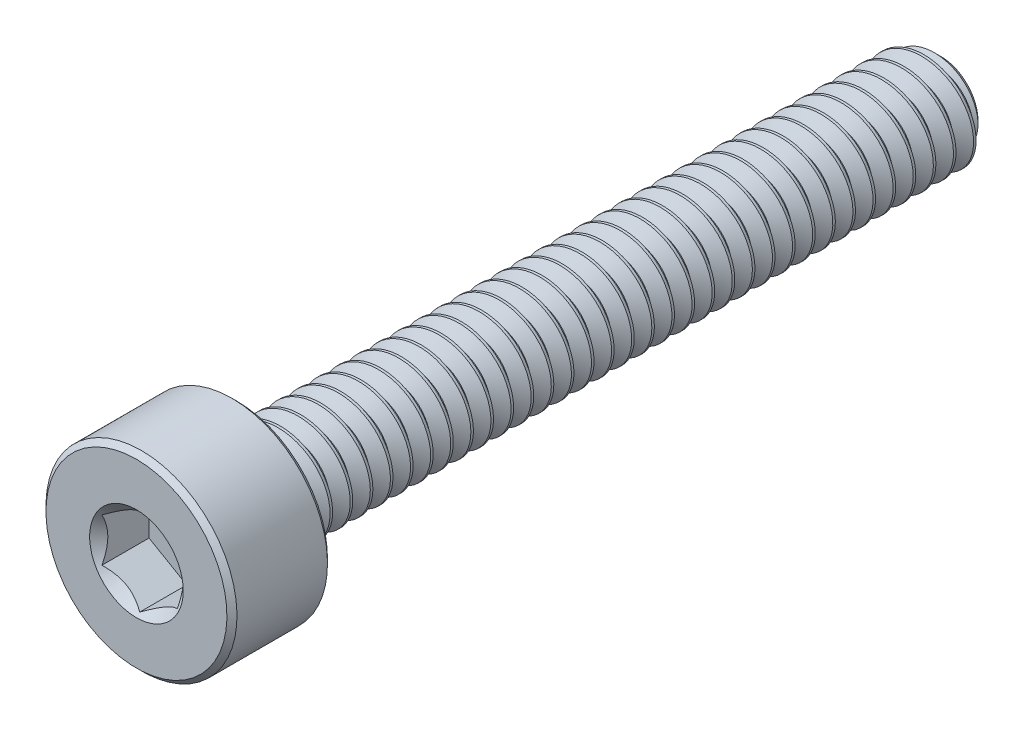
SolidWorks part; units mm, degrees
ref_plane "Front Plane" through (0, 0, 0) normal (0, 0, 1) x (1, 0, 0)
ref_plane "Top Plane" through (0, 0, 0) normal (0, 1, 0) x (1, 0, 0)
ref_plane "Right Plane" through (0, 0, 0) normal (1, 0, 0) x (0, 0, -1)
sketch "Sketch1" plane through (0, 0, 0) normal (1, 0, 0) x (0, 0, -1)
  line L0 (-8, 0) -> (8, 0) construction
  line L1 (8, 0) -> (8, 0.7402) construction
  line L2 (8, 0.7402) -> (7.7402, 1) construction
  line L3 (7.7402, 1) -> (7.7, 1) construction
  line L4 (7.7, 1) -> (-6, 1) construction
  line L5 (-6, 1) -> (-6, 1.9) construction
  line L6 (-6, 1.9) -> (-8, 1.9) construction
  line L7 (-8, 1.9) -> (-8, 0) construction
  line L8 (8, 0.7402) -> (8, 1) construction
  line L9 (7.975, 1.0433) -> (8.175, 0.6969) construction
  line L10 (8.175, 0.6969) -> (8.375, 1.0433) construction
  line L11 (8.375, 1.0433) -> (7.975, 1.0433) construction
  line L12 (8.175, 1.0433) -> (8.175, 1) construction
  line L13 (8.175, 0.6969) -> (8.175, 0.7402) construction
  line L14 (8.15, 0.7402) -> (8.2, 0.7402) construction
  line L15 (8, 1) -> (8.35, 1) construction
  line L16 (7.9875, 1.0217) -> (8.3625, 1.0217) construction
  line L17 (8, 0) -> (8, -1) construction
  line L18 (-6.1, 1.9) -> (-6, 1.8) construction
  line L19 (-7.9, 1.9) -> (-8, 1.8) construction
  line L20 (-6, 1) -> (-6, 0) construction
  line L21 (-6, 0.5) -> (-1.3333, 0.5) construction
  line L22 (-1.3333, 0.5) -> (3.3333, 0.5) construction
  line L23 (3.3333, 0.5) -> (8, 0.5) construction
  line L24 (-1.3333, 0.5) -> (-1.3333, 1) construction
  line L25 (-1.3333, 1) -> (-1.3333, 1.9) construction
  line L26 (3.3333, 0.5) -> (3.3333, 1.9) construction
  point P0 (-8, 0.75)
  point P3 (7, 1)
  point P4 (0, 0)
  point P18 (3.3333, 1)
  point P22 (8.175, 0.7402)
  point P24 (7.7, 1)
  point P25 (8.175, 1)
  point P28 (8.175, 1.0217)
  point P29 (7, -1)
  point P30 (-1.3333, 1)
  point P31 (-7, 1.9)
  point P37 (-6.35, 1.9)
  point P38 (-7.85, 1.9)
  point P45 (-1.3333, 0.5)
  point P46 (3.3333, 0.5)
  dimension "D2" = 0.05
  dimension "D7" = 0.1
  dimension "D8" = 0.1
  dimension "D9" = 0.1
  dimension "D10" = 0.05
  dimension "D11" = 0.25
  dimension "Drive Size" = 1.5
  dimension "Head Diameter" = 3.8
  dimension "Head Height" = 2
  dimension "Thread Pitch" = 0.4
  dimension "Thread Size" = 2
  dimension "Length" = 14
  dimension "D12" = 0.3
  dimension "D4" = 1
  dimension "D3" = 45
sketch "Sketch2" plane through (0, 0, 0) normal (1, 0, 0) x (0, 0, -1)
  line L0 (-8, 0) -> (-8, 1.8)
  line L1 (-7.9, 1.9) -> (-6.1, 1.9)
  line L2 (-6, 1.8) -> (-6, 1.1)
  line L4 (7.7402, 1) -> (8, 0.7402)
  line L5 (8, 0.7402) -> (8, 0)
  line L6 (-6, 1.9) -> (-8, 1.9) construction
  line L7 (8, 0) -> (-8, 0)
  line L8 (-7.9, 1.9) -> (-8, 1.8) construction
  line L10 (-7.9, 1.9) -> (-8, 1.8)
  line L14 (-6.1, 1.9) -> (-6, 1.8) construction
  line L16 (-6.1, 1.9) -> (-6, 1.8)
  line L17 (-6, 1) -> (-6, 1.9) construction
  line L19 (-5.9, 1) -> (7.7402, 1)
  line L20 (7.7, 1) -> (-6, 1) construction
  arc A1 (-6, 1.1) -> (-5.9, 1) centre (-5.9, 1.1) ccw
revolve "Revolve1" add sketch "Sketch2" angle 360 about L7
sketch "Sketch3" plane through (0, 0, 8) normal (0, 0, 1) x (1, 0, 0)
  line L1 (0.75, -0.433) -> (0.75, 0.433)
  line L2 (0.75, 0.433) -> (0, 0.866)
  line L3 (0, 0.866) -> (-0.75, 0.433)
  line L4 (-0.75, 0.433) -> (-0.75, -0.433)
  line L5 (-0.75, -0.433) -> (0, -0.866)
  line L6 (0, -0.866) -> (0.75, -0.433)
  circle A0 centre (0, 0) radius 0.75 construction
  circle A1 centre (0, 0) radius 1.9 construction
  circle A2 centre (0, 0) radius 1.9 construction
  circle A3 centre (0, 0) radius 0.866 construction
  point P13 (0, 0)
  dimension "D1" = 1.7321
extrude "Cut-Extrude1" cut sketch "Sketch3" against normal offset from surface (1 mm away) 1 up to face at (0, 1.8, 6)
sketch "Sketch4" plane through (0, 0, 8) normal (0, 0, 1) x (1, 0, 0)
  circle A0 centre (0, 0) radius 0.931
  dimension "D1" = 1.862
extrude "Cut-Extrude2" cut sketch "Sketch4" against normal up to vertex (1 mm away) draft 45 up to point (0, 1.9, 7)
sketch "Sketch11" plane through (0, 0, 0) normal (1, 0, 0) x (0, 0, -1)
  line L0 (-8, 0) -> (8, 0) construction
  line L1 (-8, 0) -> (8, 0) construction
  line L2 (-3.375, 0) -> (-3.375, 1) construction
  line L3 (7.7, 1) -> (-6, 1) construction
  line L4 (5.375, 0) -> (5.375, 1) construction
  line L6 (8, 0.7402) -> (8, 1) construction
  point P2 (-3.375, 0)
  point P3 (5.375, 0)
  dimension "D1" = 2.625
  dimension "D2" = 2.625
sketch "Sketch6" plane through (0, 0, -8) normal (0, 0, -1) x (-1, 0, 0)
  circle A0 centre (0, 0) radius 1
curve "Helix/Spiral1" pitch 0.4 height 14.4 turns 36
sketch "Sketch10" plane through (0, 0, 0) normal (1, 0, 0) x (0, 0, -1)
  line L0 (-5.9, -1.9) -> (-5.9, 1.9)
  line L5 (-8, 0) -> (8, 0) construction
  line L6 (-5.9, 1) -> (-5.9, -1) construction
  point P3 (-5.9, 0)
split "Split1" trim tools "Sketch10" bodies to split 106 resulting bodies 114 115
sketch "Sketch7" plane through (0, 0, 0) normal (1, 0, 0) x (0, 0, -1)
  line L0 (7.9875, 1.0217) -> (8.3625, 1.0217)
  line L1 (8.3625, 1.0217) -> (8.2, 0.7402)
  line L2 (8.2, 0.7402) -> (8.15, 0.7402)
  line L3 (8.15, 0.7402) -> (7.9875, 1.0217)
sweep "Cut-Sweep1" cut profiles "Sketch7" path "Helix/Spiral1"
sketch "Sketch8" plane through (0, 0, 0) normal (1, 0, 0) x (0, 0, -1)
  line L0 (-6, 0) -> (-6, 1)
  line L1 (-5.9, -1) -> (-5.9, 1) construction
  line L2 (-6, 1) -> (-5.9, 1)
  line L4 (-5.9, 1) -> (-5.3226, 0)
  line L5 (-5.3226, 0) -> (-6, 0)
  line L6 (7.7, 1) -> (-6, 1) construction
  line L7 (-8, 0) -> (8, 0) construction
  dimension "D1" = 60
revolve "Revolve2" add sketch "Sketch8" angle 360 about L5
equation "\"D2@Sketch1\" = \"Thread Pitch@Sketch1\" / 8"
equation "\"D4@Helix/Spiral1\" = \"Thread Pitch@Sketch1\""
equation "\"D7@Sketch1\" = \"Head Height@Sketch1\" * .05"
equation "\"D8@Sketch1\"=\"D7@Sketch1\""
equation "\"D9@Sketch1\"=\"D7@Sketch1\""
equation "\"D10@Sketch1\"=\"D7@Sketch1\"/2"
equation "\"D11@Sketch1\"=\"D10@Sketch1\"*5"
equation "\"D4@Sketch1\"=\"Thread Pitch@Sketch1\"*2.5"
equation "\"D12@Sketch1\"=\"Thread Pitch@Sketch1\"*.75"
equation "\"D3@Helix/Spiral1\"=\"Length@Sketch1\"+\"Thread Pitch@Sketch1\""
equation "\"D3@Sketch2\"=\"Thread Size@Sketch1\"*0.05"
equation "\"D1@Sketch11\"=\"Length@Sketch1\"*0.1875"
equation "\"D2@Sketch11\"=\"D1@Sketch11\""
equation "\"D1@Sketch4\"=\"D1@Sketch3\"*1.075"
